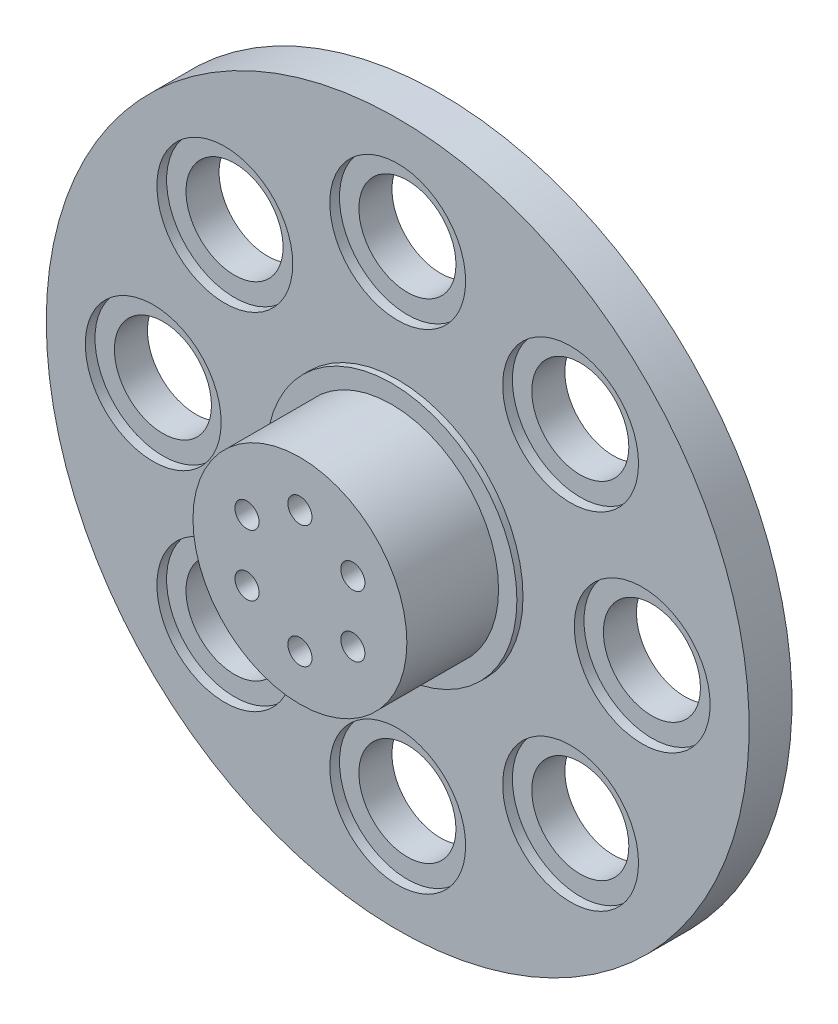
SolidWorks part; units mm, degrees
material "PETG"
ref_plane "Front Plane" through (0, 0, 0) normal (0, 0, 1) x (1, 0, 0)
ref_plane "Top Plane" through (0, 0, 0) normal (0, 1, 0) x (1, 0, 0)
ref_plane "Right Plane" through (0, 0, 0) normal (1, 0, 0) x (0, 0, -1)
sketch "Sketch1" plane through (0, 0, 0) normal (0, 0, 1) x (1, 0, 0)
  circle A0 centre (0, 0) radius 17.5
  dimension "D1" = 35
extrude "Boss-Extrude1" add sketch "Sketch1" along normal blind 15
sketch "Sketch7" plane through (0, 0, 0) normal (0, 0, -1) x (-1, 0, 0)
  circle A0 centre (0, 0) radius 20.5
  dimension "D1" = 41
extrude "Boss-Extrude3" add sketch "Sketch7" along normal blind 1
sketch "Sketch3" plane through (0, 0, -1) normal (0, 0, -1) x (-1, 0, 0)
  circle A0 centre (0, 0) radius 57.5
  dimension "D1" = 115
extrude "Boss-Extrude2" add sketch "Sketch3" along normal blind 7
sketch "Sketch4" plane through (0, 0, -8) normal (0, 0, -1) x (-1, 0, 0)
  circle A0 centre (0, 0) radius 11
  dimension "D1" = 22
extrude "Cut-Extrude1" cut sketch "Sketch4" against normal blind 7
sketch "Sketch5" plane through (0, 0, -1) normal (0, 0, -1) x (-1, 0, 0)
  circle A0 centre (0, 0) radius 7.5
  dimension "D1" = 15
extrude "Cut-Extrude2" cut sketch "Sketch5" against normal blind 0.5
sketch "Sketch6" plane through (0, 0, 15) normal (0, 0, 1) x (1, 0, 0)
  circle A0 centre (0, 10) radius 1.975
  dimension "D1" = 3.95
  dimension "D2" = 10
extrude "Cut-Extrude3" cut sketch "Sketch6" against normal blind 6
pattern_circular "CirPattern1" count 6 over 360 about axis through (0, 0, 15) along (0, 0, 1) of "Cut-Extrude3"
sketch "Sketch8" plane through (0, 0, -1) normal (0, 0, 1) x (1, 0, 0)
  circle A0 centre (0, 0) radius 40 construction
  circle A1 centre (-40, 0) radius 7.94
  circle A2 centre (-28.2843, 28.2843) radius 7.94
  circle A3 centre (0, 40) radius 7.94
  circle A4 centre (28.2843, 28.2843) radius 7.94
  circle A5 centre (40, 0) radius 7.94
  circle A6 centre (28.2843, -28.2843) radius 7.94
  circle A7 centre (0, -40) radius 7.94
  circle A8 centre (-28.2843, -28.2843) radius 7.94
  dimension "D1" = 80
  dimension "D2" = 15.88
  dimension "D3" = 8
extrude "Cut-Extrude4" cut sketch "Sketch8" against normal through all
sketch "Sketch9" plane through (0, 0, -1) normal (0, 0, 1) x (1, 0, 0)
  line L0 (0, 0) -> (0, 40) construction
  circle A0 centre (0, 40) radius 11.1125
  circle A1 centre (0, 40) radius 7.94 construction
  circle A2 centre (28.2843, 28.2843) radius 11.1125
  circle A3 centre (40, 0) radius 11.1125
  circle A4 centre (28.2843, -28.2843) radius 11.1125
  circle A5 centre (0, -40) radius 11.1125
  circle A6 centre (-28.2843, -28.2843) radius 11.1125
  circle A7 centre (-40, 0) radius 11.1125
  circle A8 centre (-28.2843, 28.2843) radius 11.1125
  point P17 (0, 0)
  point P18 (0, 0)
  dimension "D1" = 22.225
  dimension "D2" = 8
extrude "Cut-Extrude5" cut sketch "Sketch9" against normal blind 1.5875
equation "\"N\"= 21"
equation "\"R\"= 65mm"
equation "\"E\" = ROUND(\"R\" / \"N\" * 0.7, 2)"
equation "\"R_r\" = ( 1in / 2 ) / 2"
equation "\"D_p\" = 8cm"
equation "\"D1@Sketch8\"=\"D_p\""
equation "\"N_p\"= 8"
equation "\"D3@Sketch8\"=\"N_p\""
